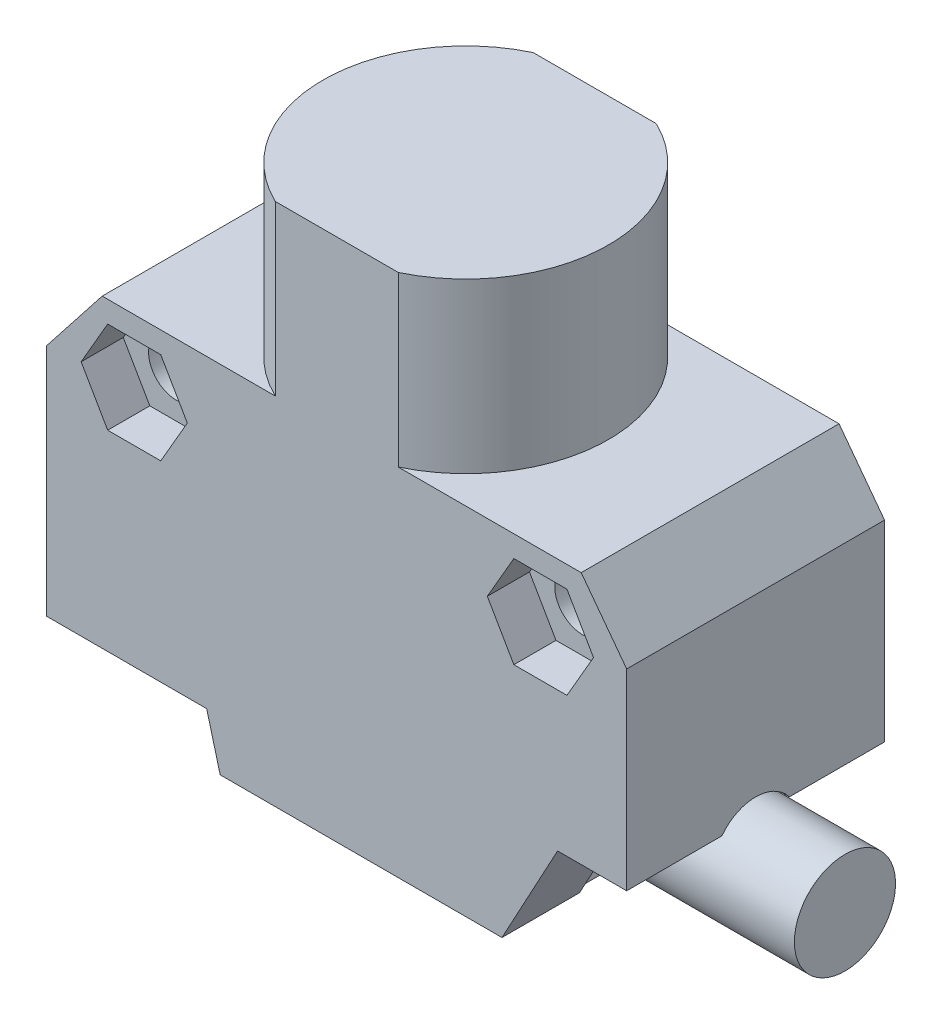
SolidWorks part; units mm, degrees
material "ABS"
ref_plane "Front Plane" through (0, 0, 0) normal (0, 0, 1) x (1, 0, 0)
ref_plane "Top Plane" through (0, 0, 0) normal (0, 1, 0) x (1, 0, 0)
ref_plane "Right Plane" through (0, 0, 0) normal (1, 0, 0) x (0, 0, -1)
sketch "Sketch1" plane through (0, 0, 0) normal (0, 1, 0) x (1, 0, 0)
  line L1 (-17.21, 7.65) -> (17.21, 7.65)
  line L2 (-17.21, 7.65) -> (-17.21, -7.65)
  line L3 (-17.21, -7.65) -> (17.21, -7.65)
  line L4 (17.21, 7.65) -> (17.21, -7.65)
  line L5 (-17.21, 7.65) -> (17.21, -7.65) construction
  line L6 (-17.21, -7.65) -> (17.21, 7.65) construction
  point P0 (0, 0)
  dimension "D1" = 34.42
  dimension "D2" = 15.3
extrude "Boss-Extrude1" add sketch "Sketch1" along normal blind 21.1
chamfer "Chamfer1" distance 3.6 distance2 2.7 1 edges at (17.21, 21.1, 0) first distance on face at (17.21, 10.55, 0)
chamfer "Chamfer2" distance 4.2 distance2 3.3 1 edges at (-17.21, 21.1, 0) first distance on face at (-17.21, 10.55, 0)
sketch "Sketch2" plane through (0, 0, 7.65) normal (0, 0, 1) x (1, 0, 0)
  line L0 (-17.21, 3) -> (-7.71, 3)
  line L1 (-17.21, 16.9) -> (-17.21, 0) construction
  line L2 (-7.71, 3) -> (-6.91, 0)
  line L3 (-17.21, 0) -> (17.21, 0) construction
  line L4 (17.21, 6.1) -> (13.11, 6.1)
  line L5 (17.21, 17.5) -> (17.21, 0) construction
  line L6 (13.11, 6.1) -> (9.81, 0)
  line L7 (-17.21, 0) -> (17.21, 0) construction
  line L8 (9.81, 0) -> (17.21, 0)
  line L9 (17.21, 0) -> (17.21, 6.1)
  line L10 (-6.91, 0) -> (-17.21, 0)
  line L11 (-17.21, 0) -> (-17.21, 3)
  dimension "D1" = 3
  dimension "D2" = 10.3
  dimension "D3" = 9.5
  dimension "D4" = 4.1
  dimension "D5" = 6.1
  dimension "D6" = 7.4
extrude "Cut-Extrude1" cut sketch "Sketch2" against normal through all
sketch "Sketch3" plane through (0, 21.1, 0) normal (0, 1, 0) x (1, 0, 0)
  line L0 (14.51, -7.65) -> (14.51, 7.65) construction
  line L1 (-13.91, 0) -> (14.51, 0) construction
  line L2 (-13.91, 7.65) -> (-13.91, -7.65) construction
  circle A0 centre (0.01, 0) radius 8.475
  dimension "D2" = 16.95
  dimension "D1" = 14.5
extrude "Boss-Extrude2" add sketch "Sketch3" along normal blind 10
sketch "Sketch4" plane through (0, 21.1, 0) normal (0, -1, 0) x (1, 0, 0)
  line L0 (-3.6373, -7.65) -> (3.6573, -7.65)
  line L1 (-3.6373, 7.65) -> (3.6573, 7.65) construction
  line L2 (-3.6373, 7.65) -> (3.6573, 7.65)
  arc A0 (-3.6373, -7.65) -> (3.6573, -7.65) centre (0.01, 0) ccw construction
  arc A1 (-3.6373, -7.65) -> (3.6573, -7.65) centre (0.01, 0) ccw
  arc A2 (3.6573, 7.65) -> (-3.6373, 7.65) centre (0.01, 0) ccw construction
  arc A3 (3.6573, 7.65) -> (-3.6373, 7.65) centre (0.01, 0) ccw
extrude "Cut-Extrude2" cut sketch "Sketch4" against normal up to next
hole_wizard "Ø0.15 (0.15) Diameter Hole1" positions "Sketch6" profile "Sketch5" hole size "Ø0.15" standard "ISO" end condition up to next
sketch "Sketch6" plane through (0, 0, 7.65) normal (0, 0, 1) x (1, 0, 0)
  line L0 (-6.91, 0) -> (9.81, 0) construction
  line L1 (-17.21, 16.9) -> (-17.21, 3) construction
  point P0 (-12.01, 17.1)
  dimension "D1" = 17.1
  dimension "D2" = 5.2
sketch "Sketch5" plane through (-12.01, 17.1, 7.65) normal (1, 0, 0) x (0, -1, 0)
  line L0 (0, 0) -> (0, 15.3)
  line L1 (0, 15.3) -> (1.65, 15.3)
  line L2 (1.65, 15.3) -> (1.65, 0)
  line L5 (1.65, 0) -> (0, 0)
  line L11 (0, -6.35) -> (0, 107.95) construction
  dimension "Thru Hole Dia." = 3.3
  dimension "Thru Hole Depth" = 15.3
hole_wizard "Ø0.15 (0.15) Diameter Hole2" positions "Sketch8" profile "Sketch7" hole size "Ø0.15" standard "ISO" end condition up to next
sketch "Sketch8" plane through (0, 0, 7.65) normal (0, 0, 1) x (1, 0, 0)
  line L0 (-13.66, 17.1) -> (24.9023, 17.1) construction
  circle A0 centre (-12.01, 17.1) radius 1.65 construction
  point P0 (12.09, 17.1)
  dimension "D1" = 24.1
sketch "Sketch7" plane through (12.09, 17.1, 7.65) normal (1, 0, 0) x (0, -1, 0)
  line L0 (0, 0) -> (0, 15.3)
  line L1 (0, 15.3) -> (1.65, 15.3)
  line L2 (1.65, 15.3) -> (1.65, 0)
  line L5 (1.65, 0) -> (0, 0)
  line L11 (0, -6.35) -> (0, 107.95) construction
  dimension "Thru Hole Dia." = 3.3
  dimension "Thru Hole Depth" = 15.3
sketch "Sketch9" plane through (0, 0, 7.65) normal (0, 0, 1) x (1, 0, 0)
  line L0 (3.6573, 21.1) -> (14.51, 21.1) construction
  line L1 (8.94, 17.1) -> (10.515, 14.372)
  line L2 (10.515, 14.372) -> (13.665, 14.372)
  line L3 (13.665, 14.372) -> (15.24, 17.1)
  line L4 (15.24, 17.1) -> (13.665, 19.828)
  line L5 (13.665, 19.828) -> (10.515, 19.828)
  line L6 (10.515, 19.828) -> (8.94, 17.1)
  line L7 (-15.16, 17.1) -> (-13.585, 14.372)
  line L8 (-13.585, 14.372) -> (-10.435, 14.372)
  line L9 (-10.435, 14.372) -> (-8.86, 17.1)
  line L10 (-8.86, 17.1) -> (-10.435, 19.828)
  line L11 (-10.435, 19.828) -> (-13.585, 19.828)
  line L12 (-13.585, 19.828) -> (-15.16, 17.1)
  line L13 (-13.91, 21.1) -> (-3.6373, 21.1) construction
  circle A0 centre (12.09, 17.1) radius 3.15 construction
  circle A1 centre (-12.01, 17.1) radius 3.15 construction
  dimension "D1" = 6.3
  dimension "D2" = 6.3
extrude "Cut-Extrude3" cut sketch "Sketch9" against normal blind 2.5
extrude "Cut-Extrude4" cut sketch "Sketch9<2>" along normal blind 2.5 from surface starting at face at (13.74, 17.1, -7.65)
sketch "Sketch9<2>" plane through (0, 0, 7.65) normal (0, 0, 1) x (1, 0, 0) same geometry as "Sketch9"
sketch "Sketch10" plane through (17.21, 0, 0) normal (1, 0, 0) x (0, 0, -1)
  line L0 (0, 17.5) -> (0, -2.6796) construction
  line L1 (3.05, 0) -> (-3.05, 0)
  line L2 (3.05, 0) -> (3.05, 6.1)
  line L3 (3.05, 6.1) -> (-3.05, 6.1)
  line L4 (-3.05, 0) -> (-3.05, 6.1)
  line L5 (3.05, 0) -> (-3.05, 6.1) construction
  line L6 (3.05, 6.1) -> (-3.05, 0) construction
  line L7 (7.65, 17.5) -> (-7.65, 17.5) construction
  line L8 (7.65, 0) -> (-7.65, 0) construction
  line L9 (7.65, 6.1) -> (-7.65, 6.1) construction
  point P0 (0, 3.05)
  dimension "D1" = 6.1
extrude "Cut-Extrude5" cut sketch "Sketch10" against normal blind 7.7
sketch "Sketch11" plane through (17.21, 0, 0) normal (1, 0, 0) x (0, 0, -1)
  line L0 (7.65, 6.1) -> (-7.65, 6.1) construction
  line L2 (2, 6.1) -> (-2, 6.1)
  line L3 (0, 6.1) -> (0, 17.5) construction
  line L4 (7.65, 17.5) -> (-7.65, 17.5) construction
  arc A0 (2, 6.1) -> (-2, 6.1) centre (0, 4.6) ccw
  point P9 (0, 7.1)
  dimension "D1" = 4
  dimension "D2" = 1
extrude "Cut-Extrude6" cut sketch "Sketch11" against normal up to surface (7.7 mm away) up to face at (9.51, 3.05, 0)
sketch "Sketch12" plane through (9.51, 0, 0) normal (1, 0, 0) x (0, 0, -1)
  line L0 (0, 0) -> (0, 7.1) construction
  line L1 (-3.05, 0) -> (3.05, 0) construction
  circle A0 centre (0, 3.8) radius 3
  arc A1 (2, 6.1) -> (-2, 6.1) centre (0, 4.6) ccw construction
  dimension "D1" = 6
  dimension "D2" = 3.8
extrude "Boss-Extrude3" add sketch "Sketch12" along normal blind 13
